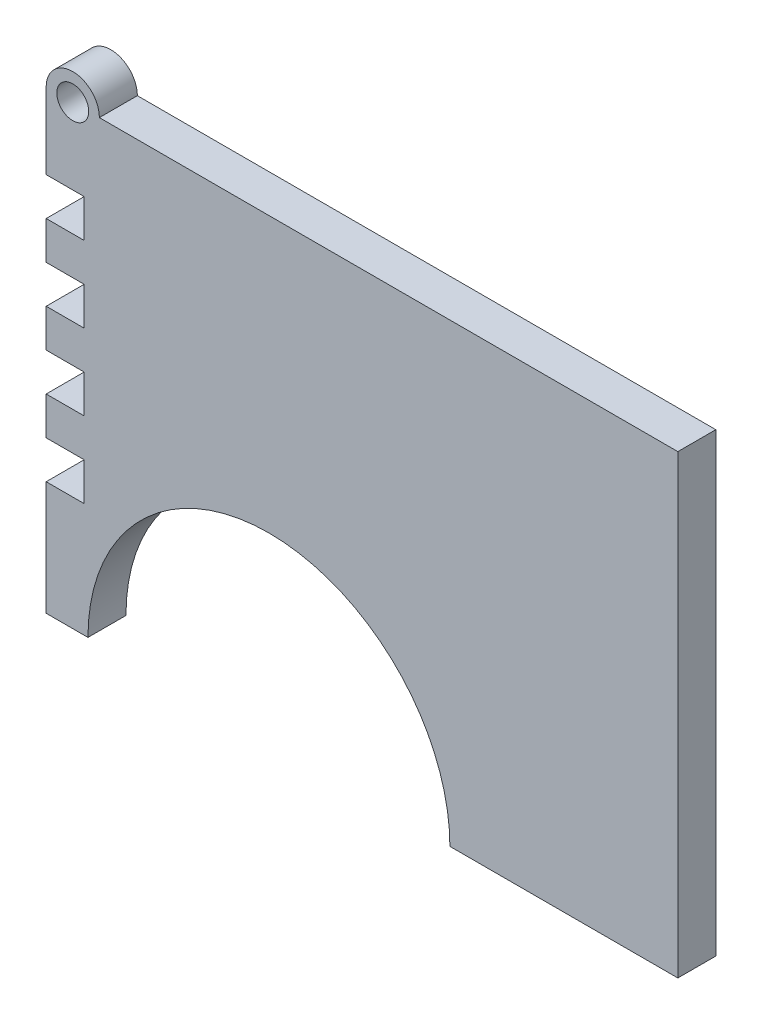
SolidWorks part; units mm, degrees
ref_plane "Plan de face" through (0, 0, 0) normal (0, 0, 1) x (1, 0, 0)
ref_plane "Plan de dessus" through (0, 0, 0) normal (0, 1, 0) x (1, 0, 0)
ref_plane "Plan de droite" through (0, 0, 0) normal (1, 0, 0) x (0, 0, -1)
sketch "Esquisse1" plane through (0, 0, 0) normal (0, 0, 1) x (1, 0, 0)
  line L2 (-78.1359, 18.8424) -> (-83.1359, 18.8424)
  line L3 (-78.1359, 13.8424) -> (-78.1359, 18.8424)
  line L4 (-83.1359, 13.8424) -> (-78.1359, 13.8424)
  line L5 (-83.1359, 8.8424) -> (-83.1359, 13.8424)
  line L6 (-78.1359, 8.8424) -> (-83.1359, 8.8424)
  line L7 (-78.1359, 3.8424) -> (-78.1359, 8.8424)
  line L8 (-83.1359, 3.8424) -> (-78.1359, 3.8424)
  line L9 (-83.1359, -1.1576) -> (-83.1359, 3.8424)
  line L10 (-78.1359, -1.1576) -> (-83.1359, -1.1576)
  line L11 (-78.1359, -1.1576) -> (-78.1359, -6.1576)
  line L12 (-83.1359, -6.1576) -> (-78.1359, -6.1576)
  line L19 (0, 13.8424) -> (0, -31.1576)
  line L21 (0, -5.7761) -> (-55, -5.7761) construction
  line L22 (-77.6359, -31.1576) -> (-30, -31.1576) construction
  line L23 (0, -31.1576) -> (-30, -31.1576)
  line L25 (-83.1359, -11.1576) -> (-78.1359, -11.1576)
  line L26 (-78.1359, -11.1576) -> (-78.1359, -16.1576)
  line L27 (-78.1359, -16.1576) -> (-83.1359, -16.1576)
  line L33 (-83.1359, -31.1576) -> (-77.6359, -31.1576)
  line L34 (-83.1359, -6.1576) -> (-83.1359, -11.1576)
  line L37 (-83.1359, 28.8424) -> (-76.1359, 28.8424) construction
  line L38 (-83.1359, 28.8424) -> (-83.1359, 18.8424)
  line L39 (-79.6359, 32.3424) -> (-77.6359, -31.1576) construction
  line L40 (-83.1359, -31.1576) -> (-83.1359, -16.1576)
  line L42 (0, 13.8424) -> (0, 28.8424)
  line L44 (0, 28.8424) -> (-76.1359, 28.8424)
  arc A4 (-30, -31.1576) -> (-77.6359, -31.1576) centre (-53.8179, -31.1576) ccw
  arc A5 (-76.1359, 28.8424) -> (-83.1359, 28.8424) centre (-79.6359, 28.8424) ccw
  circle A6 centre (-79.6359, 28.8424) radius 2.1
  dimension "D4" = 5.5
  dimension "D2" = 30
  dimension "D1" = 4.2
  dimension "D3" = 45
  dimension "D7" = 23.8179
  dimension "D6" = 5
  dimension "D8" = 5
extrude "Boss.-Extru.1" add sketch "Esquisse1" along normal blind 5
